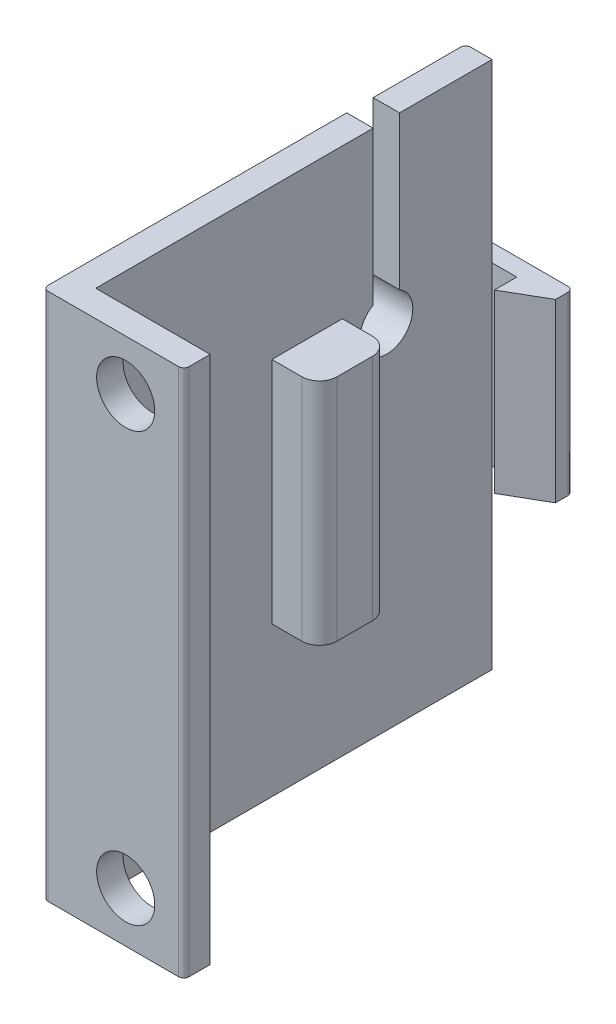
SolidWorks part; units mm, degrees
ref_plane "Front Plane" through (0, 0, 0) normal (0, 0, 1) x (1, 0, 0)
ref_plane "Top Plane" through (0, 0, 0) normal (0, 1, 0) x (1, 0, 0)
ref_plane "Right Plane" through (0, 0, 0) normal (1, 0, 0) x (0, 0, -1)
sketch "Sketch1" plane through (0, 0, 0) normal (0, 1, 0) x (1, 0, 0)
  line L0 (0, 0) -> (-2.2, 0)
  line L5 (-2.2, 0) -> (-2.2, -1.2702)
  line L6 (-2.2, -1.2702) -> (0, 0)
  dimension "D1" = 60
  dimension "D2" = 2.2
extrude "Boss-Extrude1" add sketch "Sketch1" along normal blind 5 and the other way blind 5
sketch "Sketch2" plane through (0, 0, 0) normal (0, 0, -1) x (-1, 0, 0)
  line L0 (0, 5) -> (2.2, 5) construction
  line L1 (0, -5) -> (3.6, -5)
  line L2 (0, -5) -> (0, 5)
  line L3 (0, 5) -> (3.6, 5)
  line L4 (3.6, -5) -> (3.6, 5)
  line L5 (0, -5) -> (3.6, 5) construction
  line L6 (0, 5) -> (3.6, -5) construction
  line L7 (2.2, -5) -> (2.2, 5) construction
  point P4 (1.8, 0)
  dimension "D1" = 1.4
extrude "Boss-Extrude2" add sketch "Sketch2" along normal blind 1
sketch "Sketch3" plane through (-3.6, 0, 0) normal (-1, 0, 0) x (0, 0, 1)
  line L0 (0, 0) -> (12.5427, 0) construction
  line L1 (0, -15) -> (22.5, -15)
  line L2 (0, -15) -> (0, 15)
  line L3 (0, 15) -> (22.5, 15)
  line L4 (22.5, -15) -> (22.5, 15)
  line L5 (0, -15) -> (22.5, 15) construction
  line L6 (0, 15) -> (22.5, -15) construction
  line L7 (0, -5) -> (0, 5) construction
  line L9 (0, 5) -> (-1, 5)
  line L10 (0, 5) -> (0, -5)
  line L11 (0, -5) -> (-1, -5)
  line L12 (-1, 5) -> (-1, -5)
  line L13 (0, 5) -> (-1, -5) construction
  line L14 (0, -5) -> (-1, 5) construction
  point P4 (11.25, 0)
  point P16 (-0.5, 0)
  line M6 (0, -5) -> (0, 5)
  line M7 (0, 5) -> (-1, 5)
  line M8 (-1, 5) -> (-1, -5)
  line M9 (-1, -5) -> (0, -5)
  dimension "D1" = 22.5
  dimension "D2" = 30
extrude "Boss-Extrude3" add sketch "Sketch3" along normal blind 1.5 contours L1 L4 L3 L2 M6 | M9 M6 M7 M8 region at (-3.6, 0, 11.25) region at (-3.6, 0, -0.5)
sketch "Sketch4" plane through (0, 0, 22.5) normal (0, 0, 1) x (1, 0, 0)
  line L0 (-4.35, 0) -> (3.106, 0) construction
  line L1 (-5.1, -15) -> (-3.6, -15)
  line L2 (-5.1, -15) -> (-5.1, 15)
  line L3 (-5.1, 15) -> (-3.6, 15)
  line L4 (-3.6, -15) -> (-3.6, 15)
  line L5 (-5.1, -15) -> (-3.6, 15) construction
  line L6 (-5.1, 15) -> (-3.6, -15) construction
  line L7 (-3.6, -15) -> (2.9, -15)
  line L8 (-3.6, -15) -> (-3.6, 15)
  line L9 (-3.6, 15) -> (2.9, 15)
  line L10 (2.9, -15) -> (2.9, 15)
  line L11 (-3.6, -15) -> (2.9, 15) construction
  line L12 (-3.6, 15) -> (2.9, -15) construction
  circle A0 centre (-0.4, 12.15) radius 1.65
  circle A1 centre (-0.4, -12.15) radius 1.65
  point P4 (-4.35, 0)
  point P11 (-0.35, 0)
  line M5 (-3.6, -15) -> (-3.6, 15)
  line M6 (-3.6, 15) -> (-5.1, 15)
  line M7 (-5.1, 15) -> (-5.1, -15)
  line M8 (-5.1, -15) -> (-3.6, -15)
  dimension "D4" = 3.3
  dimension "D1" = 30
  dimension "D2" = 6.5
  dimension "D3" = 3.3
  dimension "D5" = 2.85
extrude "Boss-Extrude4" add sketch "Sketch4" along normal blind 1.5 contours L7 L10 L9 M5 | M8 M5 M6 M7 region at (-4.35, 0, 22.5) region at (-0.3452, 0, 22.5)
ref_plane "Plane1" through (0, 0, 0) normal (0, 1, 0) x (1, 0, 0)
fillet "Fillet1" radius 0.3 6 edges at (-5.1, 0, -1) (-5.1, 0, 24) (-5.1, 10, 0) (-5.1, -10, 0) (2.9, 0, 24) (0, 0, -1)
sketch "Sketch5" plane through (-3.6, 0, 0) normal (1, 0, 0) x (0, 0, -1)
  line L5 (-10.5, -15) -> (-10.5, 15) construction
  line L7 (-12.5, 6.5) -> (-8.5, 6.5)
  line L8 (-12.5, 6.5) -> (-12.5, -6.5)
  line L9 (-12.5, -6.5) -> (-8.5, -6.5)
  line L10 (-8.5, 6.5) -> (-8.5, -6.5)
  line L11 (-12.5, 6.5) -> (-8.5, -6.5) construction
  line L12 (-12.5, -6.5) -> (-8.5, 6.5) construction
  line L14 (0, 15) -> (-22.5, 15) construction
  line L15 (0, 5) -> (0, 15) construction
  line L17 (0, -15) -> (-22.5, -15) construction
  point P6 (-10.5, 0)
  point P7 (-10.5, 0)
  point P12 (-10.5, 0)
  point P14 (-9.5, -4.2081)
  point P15 (0, 0)
  dimension "D1" = 13
  dimension "D2" = 4
  dimension "D3" = 10.5
extrude "Boss-Extrude5" add sketch "Sketch5" along normal blind 2.7 contours L8 L7 L10 L9
sketch "Sketch7" plane through (-3.6, 0, 0) normal (1, 0, 0) x (0, 0, -1)
  line L0 (0, 5) -> (0, 15) construction
  line L1 (0, 15) -> (-22.5, 15) construction
  line L2 (-6, 5) -> (-6, 15) construction
  line L3 (-6.75, 15) -> (-6.75, 6.299)
  line L4 (-5.25, 15) -> (-5.25, 6.299)
  line L5 (-6.75, 15) -> (-5.25, 15)
  circle A0 centre (-6, 5) radius 1.5
  circle A1 centre (-6, 5) radius 3
  line M6 (0, 15) -> (-22.5, 15)
  line M11 (-12.5, 6.5) -> (-8.5, 6.5)
  line M12 (-8.5, 6.5) -> (-8.5, -6.5)
  dimension "D1" = 3
  dimension "D6" = 1.5
  dimension "D2" = 6
  dimension "D3" = 10
  dimension "D4" = 0.75
  dimension "D5" = 1.5
extrude "Cut-Extrude1" cut sketch "Sketch7" against normal through all contours A0 | A1 L2 L5 L3 | L2 A1 L4 M6 | L2 A0 L4 A1 | A0 L2 A1 L3 region at (-3.6, 7.2008, 6.3792) region at (-3.6, 7.2008, 5.6208) region at (-3.6, 6.4079, 5.6228) region at (-3.6, 11.4842, 6.3758) region at (-3.6, 11.4842, 5.6242)
extrude "Boss-Extrude6" add sketch "Sketch7<3>" against normal blind 5 from surface contours L3 A1 L4 A0 | A1 M11 M12 region at (-3.6, 7.1019, 6.8314) region at (-3.6, 4.989, 8.7027) starting at face at (-5.1, 3.3166, 5.9333)
sketch "Sketch7<3>" plane through (-3.6, 0, 0) normal (1, 0, 0) x (0, 0, -1) same geometry as "Sketch7"
ref_plane "Plane2" through (0, 2, 0) normal (0, -1, 0) x (-1, 0, 0)
sketch "Sketch8" plane through (0, 2, 0) normal (0, -1, 0) x (-1, 0, 0)
  line L0 (10.1, -3) -> (5.1, -3) construction
  line L1 (10.1, -3) -> (7.6, -3)
  line L2 (10.1, -3) -> (10.1, -9)
  line L3 (10.1, -9) -> (7.6, -9)
  line L4 (7.6, -3) -> (7.6, -9)
  line L5 (10.1, -3) -> (7.6, -9) construction
  line L6 (10.1, -9) -> (7.6, -3) construction
  line L7 (10.1, -9) -> (10.1, -3) construction
  line L10 (5.1, -9) -> (10.1, -9) construction
  point P4 (8.85, -6)
  point P9 (7.6, -8.5981)
  point P10 (0, 0)
  point P11 (0, 0)
  point P12 (0, 0)
  point P13 (7.6, -9)
  point P14 (0, 0)
ref_axis "Axis1" through (-10.1, 5, 6) along (1, 0, 0)
ref_plane "Plane3" through (0, 5, 0) normal (0, 1, 0) x (1, 0, 0)
extrude "Cut-Extrude2" cut sketch "Sketch8" against normal up to surface (3 mm away) up to plane "Plane3"
fillet "Fillet2" radius 3 1 edges at (-7.6, 5, 8.25)
fillet "Fillet3" radius 1 1 edges at (-5.1, 2, 6)
fillet "Fillet4" radius 1 2 edges at (-0.9, 0, 12.5) (-0.9, 0, 8.5)
equation "\"WallThick\"= 1.2'thickness of wall for printer"
equation "\"dHole\"= 3.3'diameter of screw hole"
equation "\"dCable\"= 1.5"
